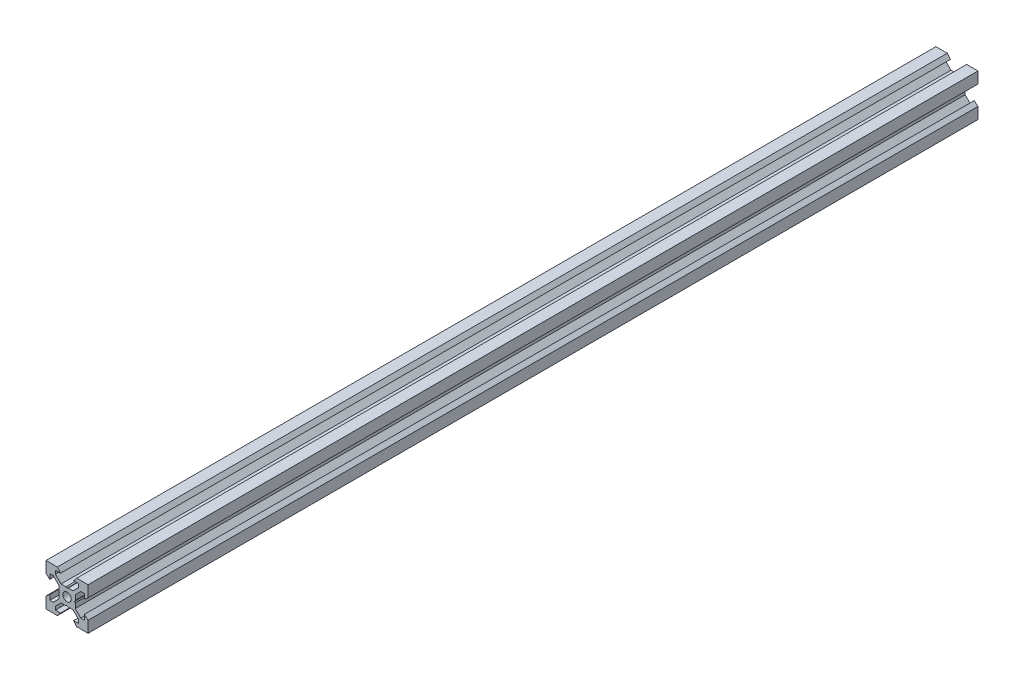
SolidWorks part; units mm, degrees
ref_plane "Front Plane" through (0, 0, 0) normal (0, 0, 1) x (1, 0, 0)
ref_plane "Top Plane" through (0, 0, 0) normal (0, 1, 0) x (1, 0, 0)
ref_plane "Right Plane" through (0, 0, 0) normal (1, 0, 0) x (0, 0, -1)
sketch "Sketch1" plane through (0, 0, 0) normal (0, 0, 1) x (1, 0, 0)
  line L0 (10, 10) -> (4.6104, 10) construction
  line L1 (10, 10) -> (10, 4.6104) construction
  line L2 (10, -10) -> (10, -4.6104) construction
  line L3 (10, -10) -> (4.6104, -10) construction
  line L4 (10, 10) -> (10, 4.6104)
  line L5 (6.5607, 5.5) -> (8.2, 5.5)
  line L6 (5.5, 8.2) -> (5.5, 6.5607)
  line L7 (10, 10) -> (4.6104, 10)
  line L8 (10, 10) -> (10, 4.6104)
  line L9 (6.5607, 5.5) -> (3.9, 2.8393)
  line L10 (5.5, 6.5607) -> (2.8393, 3.9)
  line L11 (10, 4.6104) -> (8.2, 3.1)
  line L12 (4.6104, 10) -> (3.1, 8.2)
  line L13 (8.2, 3.1) -> (8.2, 5.5)
  line L14 (3.1, 8.2) -> (5.5, 8.2)
  line L15 (-6.5607, 5.5) -> (-8.2, 5.5)
  line L16 (6.5607, -5.5) -> (8.2, -5.5)
  line L17 (3.1, -8.2) -> (5.5, -8.2)
  line L18 (8.2, -3.1) -> (8.2, -5.5)
  line L19 (4.6104, -10) -> (3.1, -8.2)
  line L20 (10, -4.6104) -> (8.2, -3.1)
  line L21 (0.5196, -3.9) -> (0, -3.6)
  line L22 (0.5196, 3.9) -> (0, 3.6)
  line L23 (3.6, 0) -> (3.9, -0.5196)
  line L24 (3.9, 0.5196) -> (3.6, 0)
  line L25 (3.9, 0.5196) -> (3.9, 2.8393)
  line L26 (2.8393, 3.9) -> (0.5196, 3.9)
  line L27 (3.9, -2.8393) -> (3.9, -0.5196)
  line L28 (2.8393, -3.9) -> (0.5196, -3.9)
  line L29 (5.5, -6.5607) -> (2.8393, -3.9)
  line L30 (6.5607, -5.5) -> (3.9, -2.8393)
  line L31 (10, -10) -> (10, -4.6104)
  line L32 (10, -10) -> (4.6104, -10)
  line L33 (5.5, -8.2) -> (5.5, -6.5607)
  line L34 (-6.5607, -5.5) -> (-8.2, -5.5)
  line L35 (10, -10) -> (10, -4.6104)
  line L36 (0, 0) -> (0, 8.2) construction
  line L37 (-10, -10) -> (-4.6104, -10) construction
  line L38 (-10, -10) -> (-10, -4.6104) construction
  line L39 (-10, 10) -> (-10, 4.6104) construction
  line L40 (-10, 10) -> (-4.6104, 10) construction
  line L41 (-10, -10) -> (-10, -4.6104)
  line L43 (-5.5, -8.2) -> (-5.5, -6.5607)
  line L44 (-10, -10) -> (-4.6104, -10)
  line L45 (-10, -10) -> (-10, -4.6104)
  line L46 (-6.5607, -5.5) -> (-3.9, -2.8393)
  line L47 (-5.5, -6.5607) -> (-2.8393, -3.9)
  line L48 (-2.8393, -3.9) -> (-0.5196, -3.9)
  line L49 (-3.9, -2.8393) -> (-3.9, -0.5196)
  line L50 (-2.8393, 3.9) -> (-0.5196, 3.9)
  line L51 (-3.9, 0.5196) -> (-3.9, 2.8393)
  line L52 (-3.9, 0.5196) -> (-3.6, 0)
  line L53 (-3.6, 0) -> (-3.9, -0.5196)
  line L54 (-0.5196, 3.9) -> (0, 3.6)
  line L55 (-0.5196, -3.9) -> (0, -3.6)
  line L56 (-10, -4.6104) -> (-8.2, -3.1)
  line L57 (-4.6104, -10) -> (-3.1, -8.2)
  line L58 (-8.2, -3.1) -> (-8.2, -5.5)
  line L59 (-3.1, -8.2) -> (-5.5, -8.2)
  line L60 (-10, -10) -> (10, -10) construction
  line L61 (-10, -10) -> (-10, 10) construction
  line L62 (-3.1, 8.2) -> (-5.5, 8.2)
  line L63 (-8.2, 3.1) -> (-8.2, 5.5)
  line L64 (-4.6104, 10) -> (-3.1, 8.2)
  line L65 (-10, 4.6104) -> (-8.2, 3.1)
  line L66 (-5.5, 6.5607) -> (-2.8393, 3.9)
  line L67 (-6.5607, 5.5) -> (-3.9, 2.8393)
  line L68 (-10, 10) -> (-10, 4.6104)
  line L69 (-10, 10) -> (-4.6104, 10)
  line L70 (-5.5, 8.2) -> (-5.5, 6.5607)
  line L71 (-10, 10) -> (10, 10) construction
  line L72 (-10, 10) -> (-10, 4.6104)
  line L73 (10, -10) -> (10, 10) construction
  line L74 (-10, -10) -> (10, 10) construction
  line L75 (-10, 10) -> (10, -10) construction
  circle A0 centre (0, 0) radius 2
  dimension "D7" = 4
  dimension "D1" = 20
  dimension "D2" = 5.3896
  dimension "D3" = 4.5
  dimension "D4" = 50
  dimension "D5" = 1.8
  dimension "D6" = 1.5104
  dimension "D8" = 5.5
  dimension "D9" = 120
  dimension "D10" = 0.3
  dimension "D11" = 2.3197
  dimension "D12" = 7.8
  dimension "D13" = 7.8
  dimension "D14" = 1.5
  dimension "D15" = 2.6607
extrude "Boss-Extrude1" add sketch "Sketch1" along normal mid plane 422.84 contours L70 L62 L64 L69 L68 L65 L63 L15 L67 L51 L52 L53 L49 L46 L34 L58 L56 L41 L44 L57 L59 L43 L47 L48 L55 L21 L28 L29 L33 L17 L19 L32 L31 L20 L18 L16 L30 L27 L23 L24 L25 L9 L5 L13 L11 L4 L7 L12 L14 L6 L10 region at (9.7172, 7.3052, 0)
